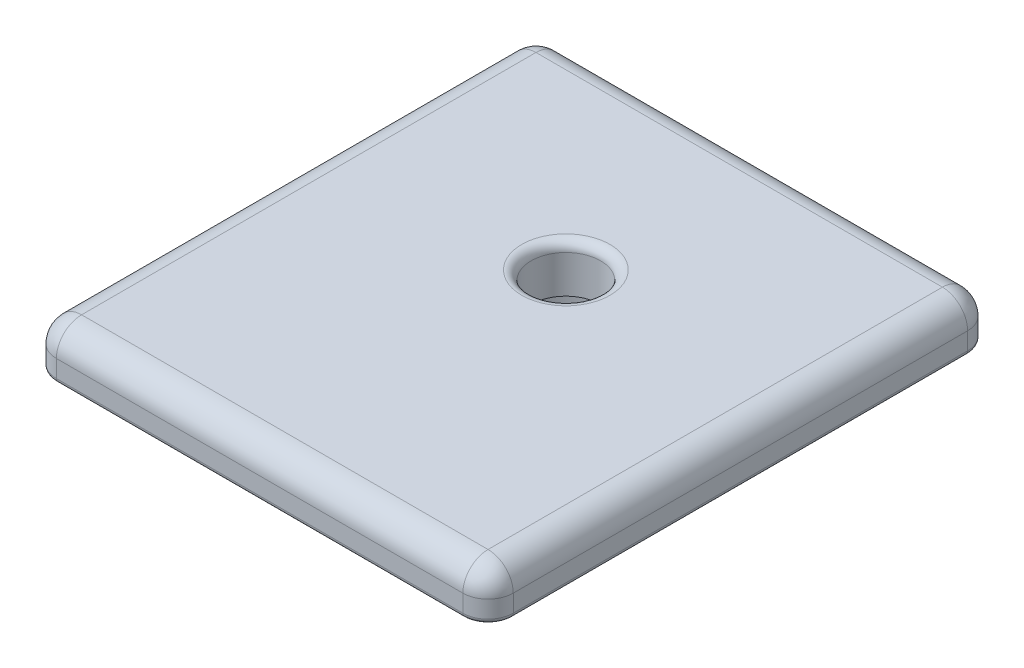
SolidWorks part; units mm, degrees
ref_plane "Спереди" through (0, 0, 0) normal (0, 0, 1) x (1, 0, 0)
ref_plane "Сверху" through (0, 0, 0) normal (0, 1, 0) x (1, 0, 0)
ref_plane "Справа" through (0, 0, 0) normal (1, 0, 0) x (0, 0, -1)
sketch "Эскиз1" plane through (0, 0, 0) normal (0, 1, 0) x (1, 0, 0)
  line L1 (-2.9642, 6.1038) -> (6.5358, 6.1038)
  line L2 (-2.9642, 6.1038) -> (-2.9642, -0.4162)
  line L3 (-2.9642, -0.4162) -> (6.5358, -0.4162)
  line L4 (6.5358, 6.1038) -> (6.5358, -0.4162)
  dimension "D1" = 9.5
  dimension "D2" = 6.52
extrude "Бобышка-Вытянуть1" add sketch "Эскиз1" along normal blind 2
sketch "Эскиз2" plane through (0, 2, 0) normal (0, 1, 0) x (1, 0, 0)
  line L0 (6.5358, 6.1038) -> (-2.9642, 6.1038) construction
  line L1 (-5.4642, 6.1038) -> (9.0358, 6.1038)
  line L2 (-5.4642, 6.1038) -> (-5.4642, -9.9162)
  line L3 (-5.4642, -9.9162) -> (9.0358, -9.9162)
  line L4 (9.0358, 6.1038) -> (9.0358, -9.9162)
  line L5 (-2.9642, -0.4162) -> (6.5358, -0.4162) construction
  line L6 (6.5358, -0.4162) -> (6.5358, 6.1038) construction
  line L7 (-2.9642, 6.1038) -> (-2.9642, -0.4162) construction
  dimension "D1" = 0
  dimension "D2" = 9.5
  dimension "D3" = 2.5
  dimension "D4" = 2.5
extrude "Бобышка-Вытянуть2" add sketch "Эскиз2" along normal blind 1.5
sketch "Эскиз3" plane through (0, 3.5, 0) normal (0, 1, 0) x (1, 0, 0)
  line L3 (9.0358, -9.9162) -> (9.0358, 6.1038) construction
  line L5 (9.0358, 6.1038) -> (-5.4642, 6.1038) construction
  line L7 (-5.4642, -9.9162) -> (9.0358, -9.9162) construction
  circle A0 centre (1.7858, -0.1962) radius 1.1
  dimension "D1" = 7.25
  dimension "D2" = 6.3
  dimension "D3" = 9.72
extrude "Вырез-Вытянуть1" cut sketch "Эскиз3" against normal through all
fillet "Скругление3" radius 0.8 4 edges at (1.7858, 3.5, -6.1038) (9.0358, 3.5, 1.9062) (1.7858, 3.5, 9.9162) (-5.4642, 3.5, 1.9062)
fillet "Скругление4" radius 0.5 4 edges at (-2.9642, 1, 0.4162) (6.5358, 1, 0.4162) (6.5358, 1, -6.1038) (-2.9642, 1, -6.1038)
fillet "Скругление7" radius 0.15 5 edges at (7.5358, 2, -6.1038) (9.0358, 2, 1.9062) (1.7858, 2, 9.9162) (-5.4642, 2, 1.9062) (-3.9642, 2, -6.1038)
fillet "Скругление8" radius 0.8 12 edges at (8.9919, 2.0439, 9.8723) (8.9919, 2.0439, -6.0599) (-5.4202, 2.0439, -6.0599) (-5.4202, 2.0439, 9.8723) (-5.2299, 3.2657, 9.6819) (-5.2299, 3.2657, -5.8695) (8.8015, 3.2657, -5.8695) (8.8015, 3.2657, 9.6819) (-5.4642, 2.425, 9.9162) (-5.4642, 2.425, -6.1038) (9.0358, 2.425, -6.1038) (9.0358, 2.425, 9.9162)
fillet "Скругление10" radius 0.3 1 edges at (1.7858, 3.5, 1.2962)
sketch "Эскиз4" plane through (0, 2, 0) normal (0, -1, 0) x (1, 0, 0)
  circle A0 centre (1.7858, 0.1962) radius 2.1
  arc A1 (2.8636, 0.4162) -> (0.708, 0.4162) centre (1.7858, 0.1962) ccw construction
  dimension "D1" = 0
extrude "Вырез-Вытянуть2" cut sketch "Эскиз4" along normal through all
fillet "Скругление11" radius 0.3 3 edges at (3.8743, 1, 0.4162) (1.7858, 0, -1.9038) (-0.3026, 1, 0.4162)
fillet "Скругление12" radius 0.15 13 edges at (4.0316, 0.0386, 0.3743) (4.1801, 0, 0.4162) (5.1102, 0, 0.4162) (6.3894, 0, 0.2697) (6.5358, 0, -2.8438) (6.3894, 0, -5.9574) (1.7858, 0, -6.1038) (-2.8177, 0, -5.9574) (-2.9642, 0, -2.8438) (-2.8177, 0, 0.2697) (-0.4599, 0.0386, 0.3743) (-0.6085, 0, 0.4162) (-1.5385, 0, 0.4162)
equation "\"D4@Эскиз2\"=\"D3@Эскиз2\""
